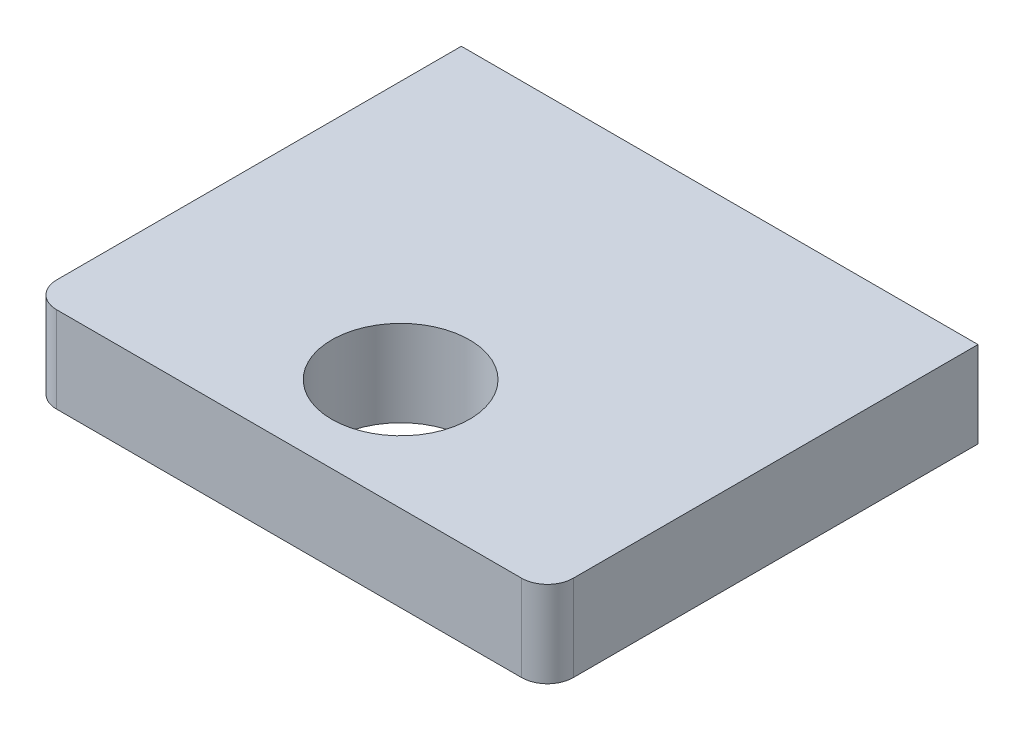
SolidWorks part; units mm, degrees
ref_plane "前视基准面" through (0, 0, 0) normal (0, 0, 1) x (1, 0, 0)
ref_plane "上视基准面" through (0, 0, 0) normal (0, 1, 0) x (1, 0, 0)
ref_plane "右视基准面" through (0, 0, 0) normal (1, 0, 0) x (0, 0, -1)
sketch "草图1" plane through (0, 0, 0) normal (0, 1, 0) x (1, 0, 0)
  line L1 (-30, 25) -> (30, 25)
  line L2 (-30, 25) -> (-30, -25)
  line L3 (-30, -25) -> (30, -25)
  line L4 (30, 25) -> (30, -25)
  line L5 (-30, 25) -> (30, -25) construction
  line L6 (-30, -25) -> (30, 25) construction
  point P0 (0, 0)
  dimension "D1" = 60
  dimension "D2" = 50
extrude "凸台-拉伸1" add sketch "草图1" along normal blind 10
sketch "草图2" plane through (0, 0, 0) normal (0, -1, 0) x (1, 0, 0)
  line L0 (-30, 25) -> (30, 25) construction
  line L2 (0, 25) -> (0, -25) construction
  line L3 (30, -25) -> (-30, -25) construction
  circle A0 centre (-18, 16.9) radius 4
  circle A1 centre (18, 16.9) radius 4
  dimension "D1" = 8
  dimension "D2" = 8.1
  dimension "D4" = 36
extrude "切除-拉伸1" cut sketch "草图2" against normal blind 0.5 contours A1 | A0
fillet "圆角1" radius 3 2 edges at (30, 5, 25) (-30, 5, 25)
sketch "草图3" plane through (0, 10, 0) normal (0, 1, 0) x (1, 0, 0)
  circle A0 centre (0, -12.05) radius 8
  dimension "D1" = 16
extrude "切除-拉伸2" cut sketch "草图3" against normal through all
